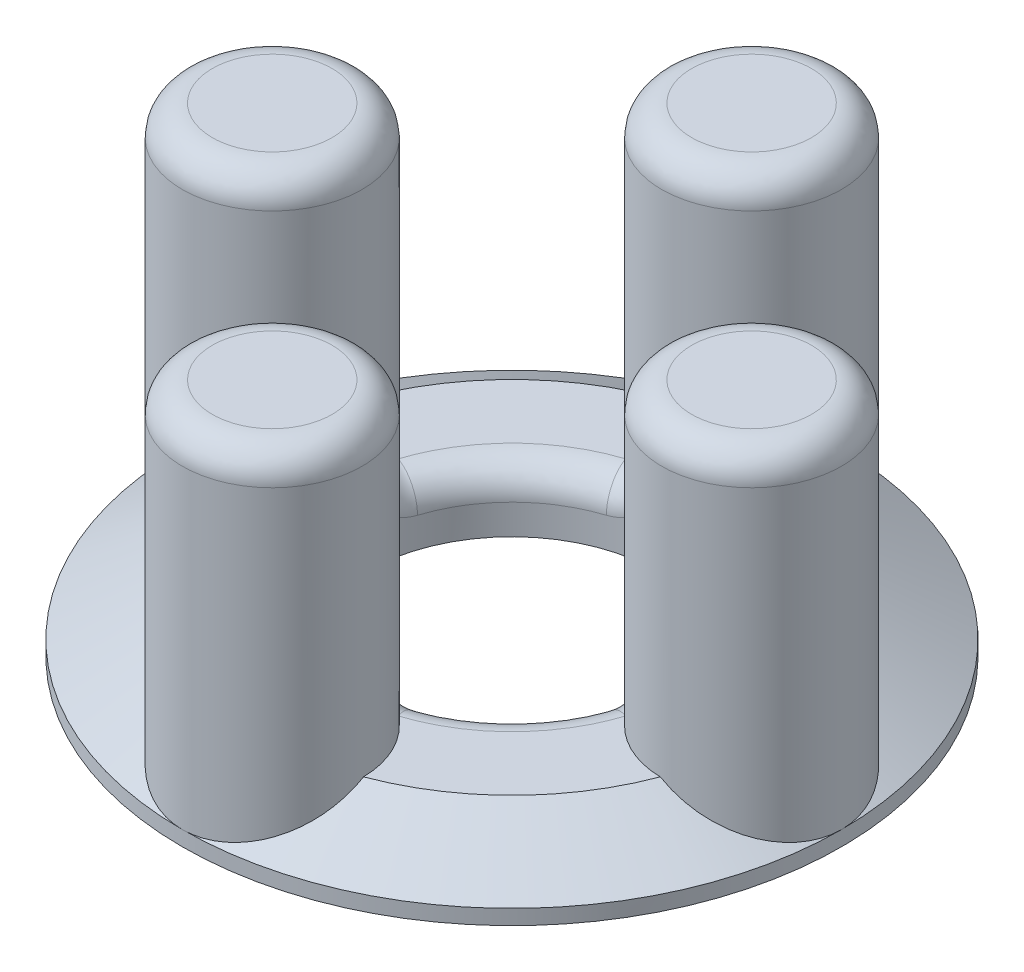
SolidWorks part; units mm, degrees
ref_plane "Alzado" through (0, 0, 0) normal (0, 0, 1) x (1, 0, 0)
ref_plane "Planta" through (0, 0, 0) normal (0, 1, 0) x (1, 0, 0)
ref_plane "Vista lateral" through (0, 0, 0) normal (1, 0, 0) x (0, 0, -1)
sketch "Croquis1" plane through (0, 0, 0) normal (0, 1, 0) x (1, 0, 0)
  circle A0 centre (0, 0) radius 11
  dimension "D1" = 22
extrude "Saliente-Extruir1" add sketch "Croquis1" along normal blind 2
sketch "Croquis2" plane through (0, 2, 0) normal (0, 1, 0) x (1, 0, 0)
  circle A0 centre (0, 0) radius 4.9
  dimension "D1" = 9.8
extrude "Cortar-Extruir1" cut sketch "Croquis2" against normal blind 4.8
sketch "Croquis5" plane through (0, 0, 0) normal (0, 0, 1) x (1, 0, 0)
  line L0 (-11, 0.5) -> (-8.5, 2)
  line L1 (-11, 2) -> (-11, 0) construction
  line L2 (11, 2) -> (-11, 2) construction
  line L3 (-8.5, 2) -> (-11, 2)
  line L4 (-11, 2) -> (-11, 0.5)
  line L5 (0, 5.563) -> (0, -3.5625) construction
  dimension "D1" = 0.5
  dimension "D2" = 8.5
revolve "Cortar-Revolución2" cut sketch "Croquis5" angle 360 about L5
sketch "Croquis3" plane through (0, 0, 0) normal (0, 1, 0) x (1, 0, 0)
  line L0 (0, -11) -> (0, 11) construction
  line L1 (-11, 0) -> (11, 0) construction
  circle A0 centre (0, 0) radius 11 construction
  circle A1 centre (0, 8) radius 3
  circle A2 centre (0, -8) radius 3
  circle A3 centre (-8, 0) radius 3
  circle A4 centre (8, 0) radius 3
  dimension "D1" = 6
  dimension "D2" = 6
extrude "Saliente-Extruir2" add sketch "Croquis3" along normal blind 12
fillet "Redondeo1" radius 1 4 edges at (0, 12, -5) (8, 12, -3) (0, 12, 5) (-8, 12, 3)
fillet "Redondeo2" radius 1 1 edges at (0, 2, 4.9)
